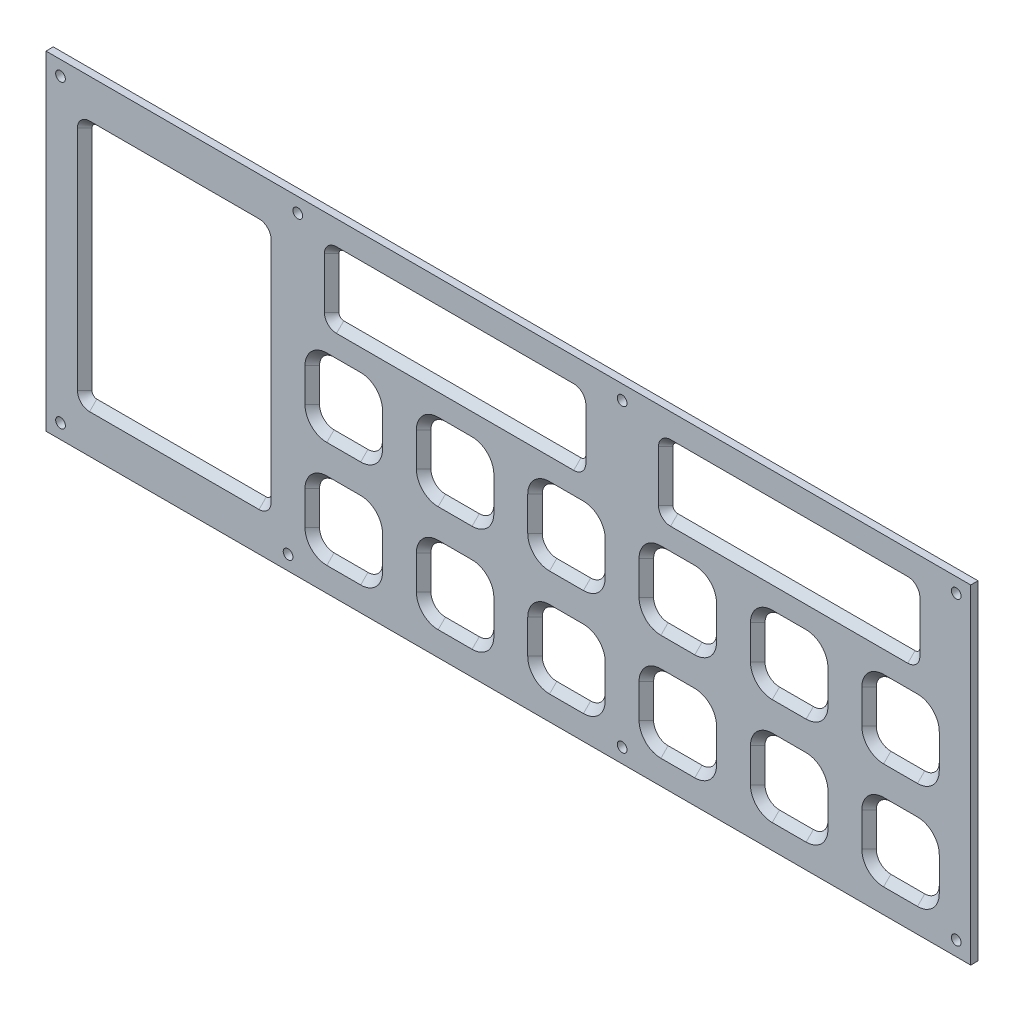
SolidWorks part; units mm, degrees
ref_plane "Front Plane" through (0, 0, 0) normal (0, 0, 1) x (1, 0, 0)
ref_plane "Top Plane" through (0, 0, 0) normal (0, 1, 0) x (1, 0, 0)
ref_plane "Right Plane" through (0, 0, 0) normal (1, 0, 0) x (0, 0, -1)
sketch "Sketch1" plane through (0, 0, 0) normal (0, 0, 1) x (1, 0, 0)
  line L1 (0, 0) -> (191, 0)
  line L2 (0, 0) -> (0, 68.0057)
  line L3 (0, 68.0057) -> (191, 68.0057)
  line L4 (191, 0) -> (191, 68.0057)
  line L5 (9, 58.5028) -> (44, 58.5028)
  line L6 (8, 57.5028) -> (8, 10.5028)
  line L7 (9, 9.5028) -> (44, 9.5028)
  line L8 (45, 57.5028) -> (45, 10.5028)
  line L32 (58, 41.5028) -> (65, 41.5028)
  line L33 (55, 38.5028) -> (55, 31.5028)
  line L34 (58, 28.5028) -> (65, 28.5028)
  line L35 (68, 38.5028) -> (68, 31.5028)
  line L41 (60, 61.5028) -> (109, 61.5028)
  line L42 (59, 60.5028) -> (59, 50.0028)
  line L43 (60, 49.0028) -> (109, 49.0028)
  line L44 (110, 60.5028) -> (110, 50.0028)
  line L48 (81, 41.5028) -> (88, 41.5028)
  line L49 (78, 38.5028) -> (78, 31.5028)
  line L50 (81, 28.5028) -> (88, 28.5028)
  line L51 (91, 38.5028) -> (91, 31.5028)
  line L52 (58, 19.5028) -> (65, 19.5028)
  line L53 (55, 16.5028) -> (55, 9.5028)
  line L54 (58, 6.5028) -> (65, 6.5028)
  line L55 (68, 16.5028) -> (68, 9.5028)
  line L56 (81, 19.5028) -> (88, 19.5028)
  line L57 (78, 16.5028) -> (78, 9.5028)
  line L58 (81, 6.5028) -> (88, 6.5028)
  line L59 (91, 16.5028) -> (91, 9.5028)
  line L60 (104, 41.5028) -> (111, 41.5028)
  line L61 (101, 38.5028) -> (101, 31.5028)
  line L62 (104, 28.5028) -> (111, 28.5028)
  line L63 (114, 38.5028) -> (114, 31.5028)
  line L64 (104, 19.5028) -> (111, 19.5028)
  line L65 (101, 16.5028) -> (101, 9.5028)
  line L66 (104, 6.5028) -> (111, 6.5028)
  line L67 (114, 16.5028) -> (114, 9.5028)
  line L68 (127, 41.5028) -> (134, 41.5028)
  line L69 (124, 38.5028) -> (124, 31.5028)
  line L70 (127, 28.5028) -> (134, 28.5028)
  line L71 (137, 38.5028) -> (137, 31.5028)
  line L72 (129, 61.5028) -> (178, 61.5028)
  line L73 (128, 60.5028) -> (128, 50.0028)
  line L74 (129, 49.0028) -> (178, 49.0028)
  line L75 (179, 60.5028) -> (179, 50.0028)
  line L76 (150, 41.5028) -> (157, 41.5028)
  line L77 (147, 38.5028) -> (147, 31.5028)
  line L78 (150, 28.5028) -> (157, 28.5028)
  line L79 (160, 38.5028) -> (160, 31.5028)
  line L80 (127, 19.5028) -> (134, 19.5028)
  line L81 (124, 16.5028) -> (124, 9.5028)
  line L82 (127, 6.5028) -> (134, 6.5028)
  line L83 (137, 16.5028) -> (137, 9.5028)
  line L84 (150, 19.5028) -> (157, 19.5028)
  line L85 (147, 16.5028) -> (147, 9.5028)
  line L86 (150, 6.5028) -> (157, 6.5028)
  line L87 (160, 16.5028) -> (160, 9.5028)
  line L88 (173, 41.5028) -> (180, 41.5028)
  line L89 (170, 38.5028) -> (170, 31.5028)
  line L90 (173, 28.5028) -> (180, 28.5028)
  line L91 (183, 38.5028) -> (183, 31.5028)
  line L92 (173, 19.5028) -> (180, 19.5028)
  line L93 (170, 16.5028) -> (170, 9.5028)
  line L94 (173, 6.5028) -> (180, 6.5028)
  line L95 (183, 16.5028) -> (183, 9.5028)
  line L96 (49.524, 6.5028) -> (49.524, 61.5028) construction
  arc A12 (55, 31.5028) -> (58, 28.5028) centre (58, 31.5028) ccw
  arc A13 (65, 28.5028) -> (68, 31.5028) centre (65, 31.5028) ccw
  arc A14 (65, 41.5028) -> (68, 38.5028) centre (65, 38.5028) cw
  arc A15 (58, 41.5028) -> (55, 38.5028) centre (58, 38.5028) ccw
  arc A24 (78, 31.5028) -> (81, 28.5028) centre (81, 31.5028) ccw
  arc A25 (88, 28.5028) -> (91, 31.5028) centre (88, 31.5028) ccw
  arc A26 (88, 41.5028) -> (91, 38.5028) centre (88, 38.5028) cw
  arc A27 (81, 41.5028) -> (78, 38.5028) centre (81, 38.5028) ccw
  arc A28 (55, 9.5028) -> (58, 6.5028) centre (58, 9.5028) ccw
  arc A29 (65, 6.5028) -> (68, 9.5028) centre (65, 9.5028) ccw
  arc A30 (65, 19.5028) -> (68, 16.5028) centre (65, 16.5028) cw
  arc A31 (58, 19.5028) -> (55, 16.5028) centre (58, 16.5028) ccw
  arc A32 (78, 9.5028) -> (81, 6.5028) centre (81, 9.5028) ccw
  arc A33 (88, 6.5028) -> (91, 9.5028) centre (88, 9.5028) ccw
  arc A34 (88, 19.5028) -> (91, 16.5028) centre (88, 16.5028) cw
  arc A35 (81, 19.5028) -> (78, 16.5028) centre (81, 16.5028) ccw
  arc A36 (101, 31.5028) -> (104, 28.5028) centre (104, 31.5028) ccw
  arc A37 (111, 28.5028) -> (114, 31.5028) centre (111, 31.5028) ccw
  arc A38 (111, 41.5028) -> (114, 38.5028) centre (111, 38.5028) cw
  arc A39 (104, 41.5028) -> (101, 38.5028) centre (104, 38.5028) ccw
  arc A40 (101, 9.5028) -> (104, 6.5028) centre (104, 9.5028) ccw
  arc A41 (111, 6.5028) -> (114, 9.5028) centre (111, 9.5028) ccw
  arc A42 (111, 19.5028) -> (114, 16.5028) centre (111, 16.5028) cw
  arc A43 (104, 19.5028) -> (101, 16.5028) centre (104, 16.5028) ccw
  arc A44 (124, 31.5028) -> (127, 28.5028) centre (127, 31.5028) ccw
  arc A45 (134, 28.5028) -> (137, 31.5028) centre (134, 31.5028) ccw
  arc A46 (134, 41.5028) -> (137, 38.5028) centre (134, 38.5028) cw
  arc A47 (127, 41.5028) -> (124, 38.5028) centre (127, 38.5028) ccw
  arc A48 (147, 31.5028) -> (150, 28.5028) centre (150, 31.5028) ccw
  arc A49 (157, 28.5028) -> (160, 31.5028) centre (157, 31.5028) ccw
  arc A50 (157, 41.5028) -> (160, 38.5028) centre (157, 38.5028) cw
  arc A51 (150, 41.5028) -> (147, 38.5028) centre (150, 38.5028) ccw
  arc A52 (124, 9.5028) -> (127, 6.5028) centre (127, 9.5028) ccw
  arc A53 (134, 6.5028) -> (137, 9.5028) centre (134, 9.5028) ccw
  arc A54 (134, 19.5028) -> (137, 16.5028) centre (134, 16.5028) cw
  arc A55 (127, 19.5028) -> (124, 16.5028) centre (127, 16.5028) ccw
  arc A56 (147, 9.5028) -> (150, 6.5028) centre (150, 9.5028) ccw
  arc A57 (157, 6.5028) -> (160, 9.5028) centre (157, 9.5028) ccw
  arc A58 (157, 19.5028) -> (160, 16.5028) centre (157, 16.5028) cw
  arc A59 (150, 19.5028) -> (147, 16.5028) centre (150, 16.5028) ccw
  arc A60 (170, 31.5028) -> (173, 28.5028) centre (173, 31.5028) ccw
  arc A61 (180, 28.5028) -> (183, 31.5028) centre (180, 31.5028) ccw
  arc A62 (180, 41.5028) -> (183, 38.5028) centre (180, 38.5028) cw
  arc A63 (173, 41.5028) -> (170, 38.5028) centre (173, 38.5028) ccw
  arc A64 (170, 9.5028) -> (173, 6.5028) centre (173, 9.5028) ccw
  arc A65 (180, 6.5028) -> (183, 9.5028) centre (180, 9.5028) ccw
  arc A66 (180, 19.5028) -> (183, 16.5028) centre (180, 16.5028) cw
  arc A67 (173, 19.5028) -> (170, 16.5028) centre (173, 16.5028) ccw
  arc A68 (60, 61.5028) -> (59, 60.5028) centre (60, 60.5028) ccw
  arc A69 (59, 50.0028) -> (60, 49.0028) centre (60, 50.0028) ccw
  arc A70 (109, 49.0028) -> (110, 50.0028) centre (109, 50.0028) ccw
  arc A71 (109, 61.5028) -> (110, 60.5028) centre (109, 60.5028) cw
  arc A84 (8, 10.5028) -> (9, 9.5028) centre (9, 10.5028) ccw
  arc A85 (44, 9.5028) -> (45, 10.5028) centre (44, 10.5028) ccw
  arc A86 (44, 58.5028) -> (45, 57.5028) centre (44, 57.5028) cw
  arc A87 (9, 58.5028) -> (8, 57.5028) centre (9, 57.5028) ccw
  arc A88 (178, 49.0028) -> (179, 50.0028) centre (178, 50.0028) ccw
  arc A89 (178, 61.5028) -> (179, 60.5028) centre (178, 60.5028) cw
  arc A90 (129, 61.5028) -> (128, 60.5028) centre (129, 60.5028) ccw
  arc A91 (128, 50.0028) -> (129, 49.0028) centre (129, 50.0028) ccw
  point P5 (8, 34.0028)
  point P10 (49.524, 34.0028)
  point P13 (45, 34.0028)
  point P19 (27.5, 19.25)
  point P22 (14.5, 19.25)
  point P146 (110, 55.2528)
  point P151 (68, 13.0028)
  point P152 (78, 13.0028)
  point P153 (68, 35.0028)
  point P154 (78, 35.0028)
  point P167 (101, 35.0028)
  point P180 (101, 13.0028)
  point P181 (91, 35.0028)
  point P182 (84.5, 49.0028)
  point P183 (84.5, 41.5028)
  point P238 (124, 35.0028)
  point P239 (124, 13.0028)
  point P240 (137, 13.0028)
  point P241 (147, 13.0028)
  point P242 (137, 35.0028)
  point P243 (147, 35.0028)
  point P256 (170, 35.0028)
  point P269 (170, 13.0028)
  point P270 (160, 35.0028)
  point P271 (153.5, 49.0028)
  point P272 (153.5, 41.5028)
  point P273 (128, 55.2528)
  point P274 (114, 35.0028)
  point P275 (114, 13.0028)
  point P276 (91, 13.0028)
  point P277 (160, 13.0028)
  point P279 (59, 61.5028)
  point P282 (59, 49.0028)
  point P287 (110, 61.5028)
  point P319 (45, 9.5028)
  point P322 (45, 58.5028)
  point P325 (8, 58.5028)
  point P331 (179, 61.5028)
  point P334 (128, 61.5028)
  point P337 (128, 49.0028)
  point P342 (0, 34.0028)
  dimension "D25" = 3
  dimension "D27" = 3
  dimension "D28" = 3
  dimension "D29" = 3
  dimension "D35" = 3
  dimension "D36" = 3
  dimension "D42" = 3
  dimension "D43" = 3
  dimension "D48" = 3
  dimension "D49" = 3
  dimension "D53" = 3
  dimension "D54" = 3
  dimension "D61" = 1
  dimension "D62" = 1
  dimension "D1" = 37
  dimension "D2" = 49
  dimension "D3" = 13
  dimension "D7" = 51
  dimension "D8" = 12.5
  dimension "D9" = 10
  dimension "D26" = 13
  dimension "D30" = 13
  dimension "D31" = 13
  dimension "D32" = 13
  dimension "D34" = 10
  dimension "D37" = 13
  dimension "D38" = 13
  dimension "D39" = 10
  dimension "D40" = 51
  dimension "D41" = 13
  dimension "D44" = 13
  dimension "D45" = 13
  dimension "D46" = 13
  dimension "D47" = 10
  dimension "D50" = 13
  dimension "D51" = 13
  dimension "D52" = 10
  dimension "D55" = 12.5
  dimension "D56" = 10
  dimension "D57" = 8
  dimension "D60" = 8
extrude "Main panel extrude" add sketch "Sketch1" along normal blind 1.5 contours L1 L4 L3 L2 A67 L92 A66 L95 A65 L94 A64 L93 A63 L88 A62 L91 A61 L90 A60 L89 A59 L84 A58 L87 A57 L86 A56 L85 A55 L80 A54 L83 A53 L82 A52 L81 A51 L76 A50 L79 A49 L78 A48 L77 A47
chamfer "Chamfers" distance 1.5 angle 45 120 edges at (183, 13.0028, 1.5) (182.1213, 18.6242, 1.5) (182.1213, 7.3815, 1.5) (176.5, 19.5028, 1.5) (176.5, 6.5028, 1.5) (170.8787, 18.6242, 1.5) (170.8787, 7.3815, 1.5) (170, 13.0028, 1.5) (160, 13.0028, 1.5) (159.1213, 18.6242, 1.5) (159.1213, 7.3815, 1.5) (153.5, 19.5028, 1.5) (153.5, 6.5028, 1.5) (147.8787, 18.6242, 1.5) (147.8787, 7.3815, 1.5) (147, 13.0028, 1.5) (160, 35.0028, 1.5) (159.1213, 40.6242, 1.5) (159.1213, 29.3815, 1.5) (153.5, 41.5028, 1.5) (153.5, 28.5028, 1.5) (147.8787, 40.6242, 1.5) (147.8787, 29.3815, 1.5) (147, 35.0028, 1.5) (183, 35.0028, 1.5) (182.1213, 40.6242, 1.5) (182.1213, 29.3815, 1.5) (176.5, 41.5028, 1.5) (176.5, 28.5028, 1.5) (170.8787, 40.6242, 1.5) (170.8787, 29.3815, 1.5) (170, 35.0028, 1.5) (179, 55.2528, 1.5) (178.7071, 61.21, 1.5) (178.7071, 49.2957, 1.5) (153.5, 61.5028, 1.5) (153.5, 49.0028, 1.5) (128.2929, 61.21, 1.5) (128.2929, 49.2957, 1.5) (128, 55.2528, 1.5) (137, 13.0028, 1.5) (136.1213, 18.6242, 1.5) (136.1213, 7.3815, 1.5) (130.5, 19.5028, 1.5) (130.5, 6.5028, 1.5) (124.8787, 18.6242, 1.5) (124.8787, 7.3815, 1.5) (124, 13.0028, 1.5) (137, 35.0028, 1.5) (136.1213, 40.6242, 1.5) (136.1213, 29.3815, 1.5) (130.5, 41.5028, 1.5) (130.5, 28.5028, 1.5) (124.8787, 40.6242, 1.5) (124.8787, 29.3815, 1.5) (124, 35.0028, 1.5) (114, 13.0028, 1.5) (113.1213, 18.6242, 1.5) (113.1213, 7.3815, 1.5) (107.5, 19.5028, 1.5) (107.5, 6.5028, 1.5) (101.8787, 18.6242, 1.5) (101.8787, 7.3815, 1.5) (101, 13.0028, 1.5) (114, 35.0028, 1.5) (113.1213, 40.6242, 1.5) (113.1213, 29.3815, 1.5) (107.5, 41.5028, 1.5) (107.5, 28.5028, 1.5) (101.8787, 40.6242, 1.5) (101.8787, 29.3815, 1.5) (101, 35.0028, 1.5) (91, 13.0028, 1.5) (90.1213, 18.6242, 1.5) (90.1213, 7.3815, 1.5) (84.5, 19.5028, 1.5) (84.5, 6.5028, 1.5) (78.8787, 18.6242, 1.5) (78.8787, 7.3815, 1.5) (78, 13.0028, 1.5) (91, 35.0028, 1.5) (90.1213, 40.6242, 1.5) (90.1213, 29.3815, 1.5) (84.5, 41.5028, 1.5) (84.5, 28.5028, 1.5) (78.8787, 40.6242, 1.5) (78.8787, 29.3815, 1.5) (78, 35.0028, 1.5) (110, 55.2528, 1.5) (109.7071, 61.21, 1.5) (109.7071, 49.2957, 1.5) (84.5, 61.5028, 1.5) (84.5, 49.0028, 1.5) (59.2929, 61.21, 1.5) (59.2929, 49.2957, 1.5) (59, 55.2528, 1.5) (68, 13.0028, 1.5) (67.1213, 18.6242, 1.5) (67.1213, 7.3815, 1.5) (61.5, 19.5028, 1.5) (61.5, 6.5028, 1.5) (55.8787, 18.6242, 1.5) (55.8787, 7.3815, 1.5) (55, 13.0028, 1.5) (68, 35.0028, 1.5) (67.1213, 40.6242, 1.5) (67.1213, 29.3815, 1.5) (61.5, 41.5028, 1.5) (61.5, 28.5028, 1.5) (55.8787, 40.6242, 1.5) (55.8787, 29.3815, 1.5) (55, 35.0028, 1.5) (45, 34.0028, 1.5) (44.7071, 58.21, 1.5) (44.7071, 9.7957, 1.5) (26.5, 58.5028, 1.5) (26.5, 9.5028, 1.5) (8.2929, 58.21, 1.5) (8.2929, 9.7957, 1.5) (8, 34.0028, 1.5)
sketch "Sketch4" plane through (0, 0, 1.5) normal (0, 0, 1) x (1, 0, 0)
  line L0 (0, 0) -> (0, 68.0057) construction
  line L1 (0, 68.0057) -> (191, 68.0057) construction
  line L2 (0, 0) -> (191, 0) construction
  line L3 (191, 0) -> (191, 68.0057) construction
  line L4 (57.5, 60.5028) -> (46.5, 57.5028) construction
  line L6 (46.5, 10.5028) -> (53.5, 9.5028) construction
  line L8 (111.5, 60.5028) -> (126.5, 60.5028) construction
  circle A0 centre (3, 65.0057) radius 1
  circle A1 centre (3, 3) radius 1
  circle A2 centre (188, 3) radius 1
  circle A3 centre (188, 65.0057) radius 1
  circle A4 centre (52, 65.0057) radius 1
  circle A5 centre (50, 3) radius 1
  circle A7 centre (119, 3) radius 1
  circle A8 centre (119, 65.0057) radius 1
  circle A9 centre (119, 3) radius 1
  point P16 (0, 0)
  point P28 (0, 0)
  point P29 (52, 59.0028)
  point P32 (50, 10.0028)
  point P36 (0, 0)
  point P37 (0, 0)
  point P38 (0, 0)
  point P39 (0, 0)
  point P41 (0, 0)
  point P45 (119, 60.5028)
  dimension "D1" = 2
  dimension "D2" = 3
  dimension "D3" = 3
  dimension "D4" = 3
  dimension "D5" = 3
extrude "Screwholes" cut sketch "Sketch4" against normal through all both and the other way through all contours A1 | A5 | A0 | A7 | A2 | A3 | A8 | A4
